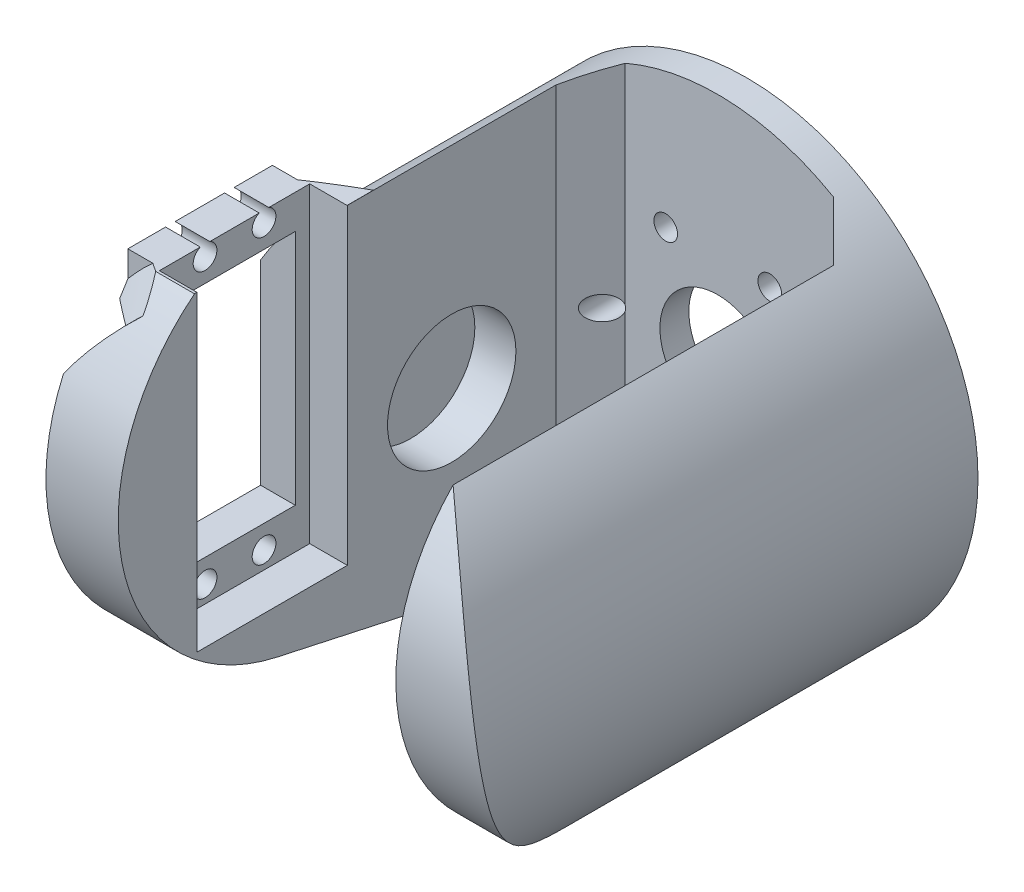
SolidWorks part; units mm, degrees
ref_plane "Front Plane" through (0, 0, 0) normal (1, 0, 0) x (0, 1, 0)
ref_plane "Top Plane" through (0, 0, 0) normal (0, 0, 1) x (0, 1, 0)
ref_plane "Right Plane" through (0, 0, 0) normal (0, 1, 0) x (-1, 0, 0)
sketch "Sketch3" plane through (0, 0, 0) normal (0, 0, 1) x (0, 1, 0)
  circle A0 centre (0, 18) radius 2.05
  circle A1 centre (15.5885, 9) radius 2.05
  circle A2 centre (15.5885, -9) radius 2.05
  circle A3 centre (0, -18) radius 2.05
  circle A4 centre (-15.5885, -9) radius 2.05
  circle A5 centre (-15.5885, 9) radius 2.05
  circle A6 centre (0, 0) radius 18 construction
  circle A9 centre (0, 0) radius 10
  circle A10 centre (0, 0) radius 40
  point P15 (0, 0)
  dimension "D2" = 4.1
  dimension "D4" = 36
  dimension "D5" = 20
  dimension "D6" = 80
  dimension "D1" = 18
  dimension "D3" = 6
extrude "Boss-Extrude1" add sketch "Sketch3" along normal blind 5
sketch "Sketch4" plane through (0, 0, 0) normal (1, 0, 0) x (0, 1, 0)
  line L0 (-40, 5) -> (-28.1874, 59.125)
  line L1 (40, 5) -> (40, 60)
  line L2 (0, 0) -> (0, 31.9351) construction
  line L3 (-40, 5) -> (40, 5)
  arc A0 (-28.1874, 59.125) -> (40, 60) centre (6.0077, 51.6621) cw
  dimension "D1" = 55
  dimension "D2" = 35
  dimension "D3" = 12.312
extrude "Boss-Extrude2" add sketch "Sketch4" along normal mid plane 82
sketch "Sketch5" plane through (0, 0, 0) normal (0, 0, 1) x (0, 1, 0)
  line L0 (-20.2423, 34.5) -> (20.2423, 34.5)
  line L1 (-56.2163, 44.9625) -> (56.2163, 44.9625)
  line L2 (-56.2163, 44.9625) -> (-56.2163, -44.9625)
  line L3 (-56.2163, -44.9625) -> (56.2163, -44.9625)
  line L4 (56.2163, 44.9625) -> (56.2163, -44.9625)
  line L5 (-56.2163, 44.9625) -> (56.2163, -44.9625) construction
  line L6 (-56.2163, -44.9625) -> (56.2163, 44.9625) construction
  arc A0 (-20.2423, 34.5) -> (20.2423, 34.5) centre (0, 0) ccw
  dimension "D1" = 80
  dimension "D2" = 34.5
extrude "Cut-Extrude1" cut sketch "Sketch5" along normal blind 100
sketch "Sketch6" plane through (0, 0, 0) normal (0, 0, 1) x (0, 1, 0)
  line L0 (-13.8577, -26) -> (13.8577, -26)
  line L1 (13.8577, 26) -> (30.3974, 26) construction
  line L2 (-44, 0) -> (44, 0) construction
  line L3 (0, -45.1) -> (0, 45.1) construction
  line L4 (-13.8577, 26) -> (13.8577, 26) construction
  line L5 (13.8577, -26) -> (30.3974, -26)
  line L6 (-13.8577, 26) -> (-30.3974, 26) construction
  line L7 (-13.8577, -26) -> (-30.3974, -26)
  line L8 (-33.4066, 22) -> (33.4066, 22)
  line L9 (-20.2423, 34.5) -> (20.2423, 34.5)
  circle A0 centre (0, 0) radius 26 construction
  arc A1 (-28.1874, 28.3808) -> (-28.1874, -28.3808) centre (0, 0) ccw construction
  arc A8 (-28.1874, -28.3808) -> (20.2423, 34.5) centre (0, 0) ccw construction
  arc A13 (30.3974, -26) -> (33.4066, 22) centre (0, 0) ccw
  arc A14 (20.2423, 34.5) -> (-20.2423, 34.5) centre (0, 0) ccw
  arc A15 (-33.4066, 22) -> (-30.3974, -26) centre (0, 0) ccw
  dimension "D1" = 52
  dimension "D2" = 22
  dimension "D3" = 27.7153
  dimension "D4" = 12.5
extrude "Cut-Extrude2" cut sketch "Sketch6" along normal blind 82 from offset 5
sketch "Sketch7" plane through (0, 0, 0) normal (1, 0, 0) x (0, 1, 0)
  line L0 (20.2423, 0) -> (-20.2423, 0) construction
  circle A0 centre (-3, 29) radius 11.1
  dimension "D1" = 22.2
  dimension "D2" = 29
  dimension "D3" = 3
extrude "Cut-Extrude3" cut sketch "Sketch7" against normal blind 7.1 from surface at -22 starting at face at (-22, -6.5425, 39.4494)
sketch "Sketch9" plane through (0, 0, 0) normal (1, 0, 0) x (0, 1, 0)
  line L0 (-40, 0) -> (40, 0) construction
  line L1 (33.375, 47.4981) -> (26.625, 47.4981)
  line L2 (33.375, 47.4981) -> (33.375, 72.4981)
  line L3 (33.375, 72.4981) -> (26.625, 72.4981)
  line L4 (26.625, 47.4981) -> (26.625, 72.4981)
  line L5 (33.375, 47.4981) -> (26.625, 72.4981) construction
  line L6 (33.375, 72.4981) -> (26.625, 47.4981) construction
  point P0 (30, 59.9981)
  dimension "D1" = 59.9981
  dimension "D2" = 25
  dimension "D3" = 6.75
  dimension "D4" = 30
extrude "Boss-Extrude3" add sketch "Sketch9" against normal blind 12.5 from surface at -22 starting at face at (-22, -3, 17.9)
sketch "Sketch8" plane through (0, 0, 0) normal (1, 0, 0) x (0, 1, 0)
  line L0 (-3, 60.05) -> (0.7243, 60.05) construction
  line L1 (27.5, 70.55) -> (-13.5, 70.55)
  line L2 (27.5, 70.55) -> (27.5, 49.55)
  line L3 (27.5, 49.55) -> (-13.5, 49.55)
  line L4 (-13.5, 70.55) -> (-13.5, 49.55)
  line L5 (27.5, 70.55) -> (-13.5, 49.55) construction
  line L6 (27.5, 49.55) -> (-13.5, 70.55) construction
  line L7 (-17.5, 65.15) -> (-17.5, 54.95) construction
  line L8 (7, 60.05) -> (7, 62.3976) construction
  circle A0 centre (-3, 60.05) radius 5 construction
  circle A1 centre (-17.5, 65.15) radius 2.05
  circle A2 centre (-17.5, 54.95) radius 2.05
  circle A3 centre (31.5, 54.95) radius 2.05
  circle A4 centre (31.5, 65.15) radius 2.05
  point P4 (7, 60.05)
  point P13 (-17.5, 60.05)
  dimension "D1" = 10
  dimension "D5" = 4.1
  dimension "D6" = 4.1
  dimension "D2" = 31.05
  dimension "D3" = 41
  dimension "D4" = 21
  dimension "D7" = 10.2
  dimension "D8" = 49
  dimension "D9" = 14.5
extrude "Cut-Extrude5" cut sketch "Sketch8" against normal blind 50
chamfer "Chamfer1" distance 5 angle 45 4 edges at (-32.1757, 26.625, 47.4981) (-32.1757, 26.625, 72.4981) (-26.1682, 30.2527, 72.4981) (-26.1682, 30.2527, 47.4981)
chamfer "Chamfer2" distance 6 angle 45 2 edges at (26, 0, 5) (-22, 0, 5)
sketch "Sketch10" plane through (0, 0, 0) normal (1, 0, 0) x (0, 1, 0)
  circle A0 centre (-3, 29) radius 11.1
extrude "Cut-Extrude6" cut sketch "Sketch10" along normal blind 7 from surface at 26 starting at face at (26, -6.6751, 44.824)
sketch "Sketch11" plane through (0, 0, 0) normal (1, 0, 0) x (0, 1, 0)
  line L0 (27.5, 70.55) -> (-13.5, 49.55) construction
  line L1 (-20.5, 73.05) -> (34.5, 73.05)
  line L2 (-20.5, 73.05) -> (-20.5, 47.05)
  line L3 (-20.5, 47.05) -> (34.5, 47.05)
  line L4 (34.5, 73.05) -> (34.5, 47.05)
  line L5 (-20.5, 73.05) -> (34.5, 47.05) construction
  line L6 (-20.5, 47.05) -> (34.5, 73.05) construction
  point P0 (7, 60.05)
  dimension "D1" = 55
  dimension "D2" = 26
extrude "Cut-Extrude7" cut sketch "Sketch11" against normal blind 6.5 from surface at -22 starting at face at (-22, 10.3334, 49.9386)
